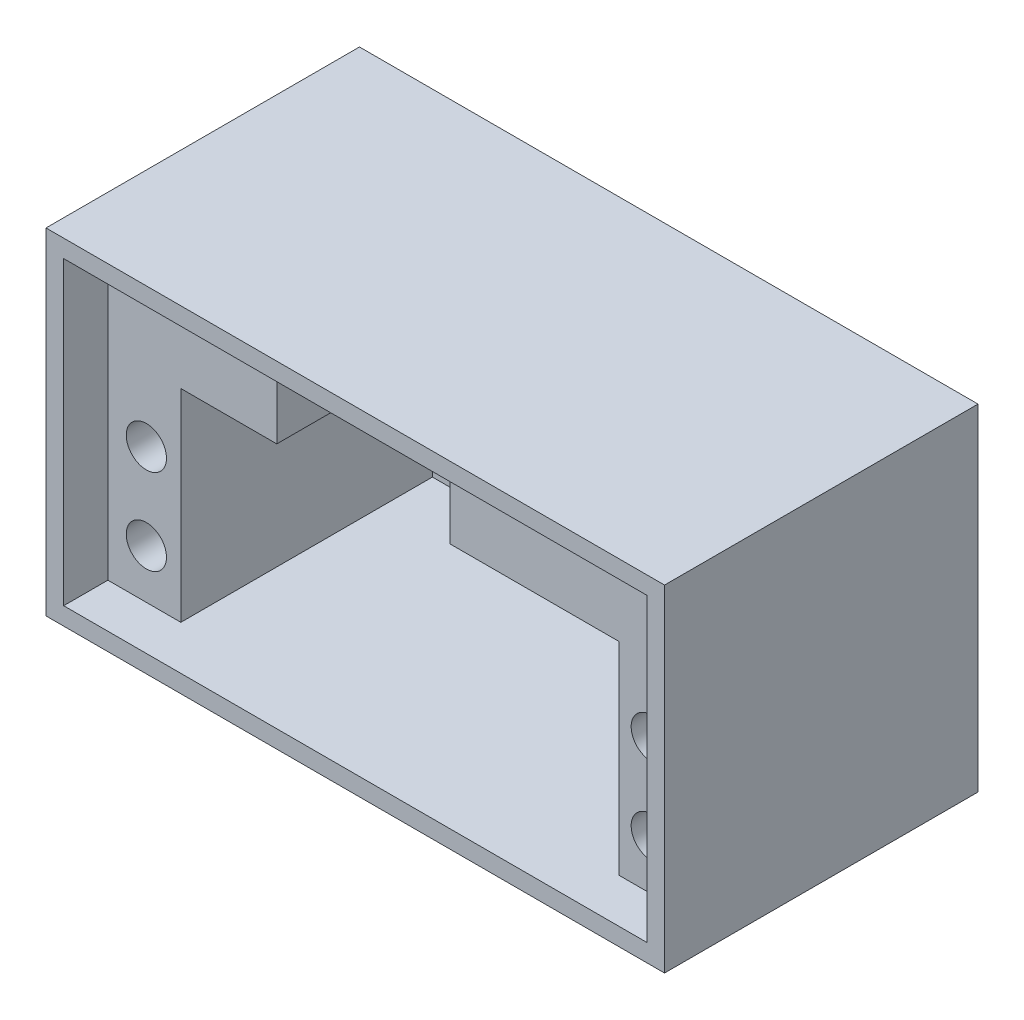
SolidWorks part; units mm, degrees
ref_plane "Front Plane" through (0, 0, 0) normal (0, 0, 1) x (1, 0, 0)
ref_plane "Top Plane" through (0, 0, 0) normal (0, 1, 0) x (1, 0, 0)
ref_plane "Right Plane" through (0, 0, 0) normal (1, 0, 0) x (0, 0, -1)
sketch "Sketch1" plane through (0, 0, 0) normal (0, 0, 1) x (1, 0, 0)
  line L0 (-20.45, 10.4) -> (-20.45, -10.4)
  line L1 (-28.9, 10.4) -> (28.9, 10.4)
  line L2 (-28.9, 10.4) -> (-28.9, -10.4)
  line L3 (-28.9, -10.4) -> (28.9, -10.4)
  line L4 (28.9, 10.4) -> (28.9, -10.4)
  line L5 (-28.9, 10.4) -> (28.9, -10.4) construction
  line L6 (-28.9, -10.4) -> (28.9, 10.4) construction
  line L7 (28.9, -10.4) -> (37.05, -10.4)
  line L8 (28.9, -10.4) -> (28.9, 12.5)
  line L9 (28.9, 12.5) -> (37.05, 12.5)
  line L10 (37.05, -10.4) -> (37.05, 12.5)
  line L11 (-28.9, 10.4) -> (28.9, 10.4)
  line L12 (-28.9, 10.4) -> (-28.9, 12.5)
  line L13 (-28.9, 12.5) -> (28.9, 12.5)
  line L14 (28.9, 10.4) -> (28.9, 12.5)
  line L15 (20.45, 10.4) -> (20.45, -10.4)
  line L16 (20.45, 0) -> (-20.45, 0) construction
  line L17 (24.55, 4.85) -> (24.55, -4.85) construction
  line L18 (-24.55, 4.85) -> (-24.55, -4.85) construction
  line L19 (24.55, 0) -> (-24.55, 0) construction
  line L20 (-9.8, 12.5) -> (-9.8, 23.6)
  line L21 (-9.8, 23.6) -> (9.8, 23.6)
  line L22 (9.8, 23.6) -> (9.8, 12.5)
  line L23 (-20.65, 12.5) -> (-20.65, -10.4)
  line L24 (-28.9, 12.5) -> (-9.8, 12.5)
  line L25 (-28.9, 12.5) -> (-28.9, 23.6)
  line L26 (-28.9, 23.6) -> (-9.8, 23.6)
  line L27 (-9.8, 12.5) -> (-9.8, 23.6)
  line L28 (37.05, 12.5) -> (9.8, 12.5)
  line L29 (37.05, 12.5) -> (37.05, 23.6)
  line L30 (37.05, 23.6) -> (9.8, 23.6)
  line L31 (9.8, 12.5) -> (9.8, 23.6)
  line L32 (-30.9, 25.6) -> (39.05, 25.6)
  line L33 (-30.9, 25.6) -> (-30.9, -12.4)
  line L34 (-30.9, -12.4) -> (39.05, -12.4)
  line L35 (39.05, 25.6) -> (39.05, -12.4)
  line L36 (20.45, 12.5) -> (20.45, 10.4)
  circle A0 centre (-24.55, 4.85) radius 2.275
  circle A1 centre (-24.55, -4.85) radius 2.275
  circle A2 centre (24.55, 4.85) radius 1.7
  circle A3 centre (24.55, -4.85) radius 1.7
  circle A4 centre (32.55, 4.85) radius 2.275
  circle A5 centre (32.55, -4.85) radius 2.275
  point P0 (0, 0)
  point P16 (0, 0)
  point P27 (0, 0)
  point P30 (0, 23.6)
  dimension "D7" = 4.55
  dimension "D8" = 4.55
  dimension "D9" = 4.55
  dimension "D10" = 4.55
  dimension "D14" = 3.4
  dimension "D15" = 3.4
  dimension "D1" = 49.1
  dimension "D2" = 19.6
  dimension "D3" = 34
  dimension "D4" = 20.8
  dimension "D5" = 2.1
  dimension "D6" = 8
  dimension "D11" = 57.8
  dimension "D12" = 40.9
  dimension "D13" = 9.7
  dimension "D16" = 8.15
  dimension "D17" = 2
  dimension "D18" = 2
  dimension "D19" = 2
  dimension "D20" = 2
  dimension "D21" = 0.2
extrude "Boss-Extrude1" add sketch "Sketch1" against normal blind 28.45 contours L26 L25 L13 L20 | L23 L13 L12 L1 | L23 L1 L2 L3 A1 A0 | L29 L30 L22 L13 L28 L9 | L7 L10 L9 L8 L4 A5 A4 region at (-24.8276, 0, 0) region at (-24.775, 11.45, 0) region at (33.0647, 1.2716, 0) region at (23.425, 18.05, 0) region at (-19.35, 18.05, 0)
extrude "Boss-Extrude2" add sketch "Sketch1<4>" against normal blind 2 from surface contours L26 L25 L13 L20 | L29 L30 L22 L13 L28 L9 | L36 L13 L23 L11 L1 | L23 L13 L12 L1 | L23 L1 L2 L3 A1 A0 | A0 | A1 | L15 L1 L0 L3 | L11 L23 L3 L0 | L11 L15 L3 L4 A3 A2 | A2 | A3 | L28 L36 L11 L8 | L7 L10 L9 L8 L4 A5 A4 | A4 | A5 region at (0, 0, 0) region at (-0.1, 11.45, 0) region at (-20.55, 0, 0) region at (24.675, 11.45, 0) region at (24.6894, 0, 0) region at (-24.8276, 0, 0) region at (-24.775, 11.45, 0) region at (33.0647, 1.2716, 0) region at (23.425, 18.05, 0) region at (-19.35, 18.05, 0) region at (-24.55, 4.85, 0) region at (-24.55, -4.85, 0) region at (24.55, 4.85, 0) region at (24.55, -4.85, 0) region at (32.55, 4.85, 0) region at (32.55, -4.85, 0) starting at face at (25.25, 8.5667, -28.45)
sketch "Sketch1<4>" plane through (0, 0, 0) normal (0, 0, 1) x (1, 0, 0) same geometry as "Sketch1"
extrude "Boss-Extrude3" add sketch "Sketch1<5>" against normal up to surface (30.45 mm away) from surface contours L35 L32 L33 L34 L30 L29 L10 L7 L3 L2 L12 L25 L26 L21 region at (4.075, 24.8039, 0) up to face at (2.0375, 12.325, -30.45) starting at face at (-19.7833, 8.5667, 0)
sketch "Sketch1<5>" plane through (0, 0, 0) normal (0, 0, 1) x (1, 0, 0) same geometry as "Sketch1"
extrude "Boss-Extrude4" add sketch "Sketch1<6>" along normal blind 5 from surface contours L35 L32 L33 L34 L30 L29 L10 L7 L3 L2 L12 L25 L26 L21 region at (4.075, 24.8039, 0) starting at face at (2.0625, 9.55, 0)
sketch "Sketch1<6>" plane through (0, 0, 0) normal (0, 0, 1) x (1, 0, 0) same geometry as "Sketch1"
